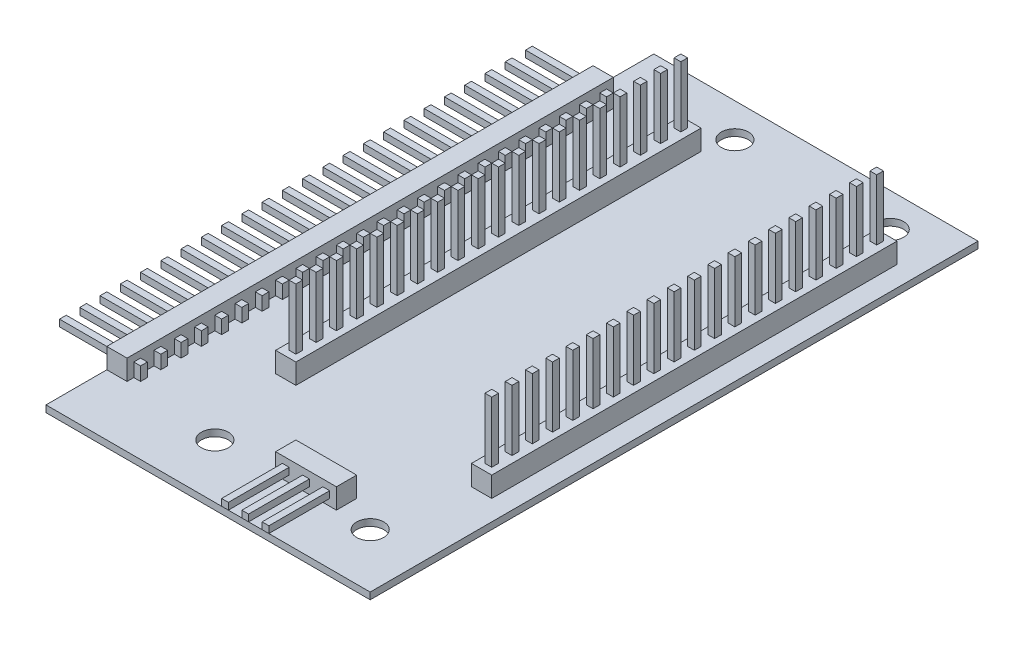
SolidWorks part; units mm, degrees
ref_plane "Front Plane" through (0, 0, 0) normal (0, 0, 1) x (1, 0, 0)
ref_plane "Top Plane" through (0, 0, 0) normal (0, 1, 0) x (1, 0, 0)
ref_plane "Right Plane" through (0, 0, 0) normal (1, 0, 0) x (0, 0, -1)
sketch "Sketch1" plane through (0, 0, 0) normal (0, 1, 0) x (1, 0, 0)
  line L1 (-19.05, 35.7188) -> (19.05, 35.7188)
  line L2 (-19.05, 35.7188) -> (-19.05, -35.7187)
  line L3 (-19.05, -35.7187) -> (19.05, -35.7187)
  line L4 (19.05, 35.7188) -> (19.05, -35.7187)
  line L5 (-19.05, 35.7188) -> (19.05, -35.7187) construction
  line L6 (-19.05, -35.7187) -> (19.05, 35.7188) construction
  point P0 (0, 0)
  dimension "D1" = 38.1
  dimension "D2" = 71.4375
extrude "Boss-Extrude1" add sketch "Sketch1" along normal blind 0.7937
sketch "Sketch2" plane through (0, 0.7937, 0) normal (0, 1, 0) x (1, 0, 0)
  line L0 (0, 0) -> (-19.05, 0) construction
  line L1 (-19.05, 35.7188) -> (-19.05, -35.7187) construction
  line L2 (-19.05, 4.7625) -> (-25.5985, 4.7625) construction
  line L3 (-15.875, 0.7937) -> (-25.4, 0.7937)
  line L4 (-15.875, 0.7937) -> (-15.875, 1.5875)
  line L5 (-15.875, 1.5875) -> (-25.4, 1.5875)
  line L6 (-25.4, 0.7937) -> (-25.4, 1.5875)
  line L7 (-25.4, 3.175) -> (-15.875, 3.175)
  line L8 (-25.4, 3.175) -> (-25.4, 3.9687)
  line L9 (-25.4, 3.9687) -> (-15.875, 3.9687)
  line L10 (-15.875, 3.175) -> (-15.875, 3.9687)
  line L11 (-15.875, 7.9375) -> (-25.4, 7.9375)
  line L12 (-25.4, 8.7312) -> (-25.4, 7.9375)
  line L13 (-15.875, 8.7312) -> (-25.4, 8.7312)
  line L14 (-15.875, 8.7312) -> (-15.875, 7.9375)
  line L15 (-25.4, 5.5562) -> (-15.875, 5.5562)
  line L16 (-15.875, 6.35) -> (-15.875, 5.5562)
  line L17 (-25.4, 6.35) -> (-15.875, 6.35)
  line L18 (-25.4, 6.35) -> (-25.4, 5.5562)
  line L19 (-19.05, 9.525) -> (-25.9028, 9.525) construction
  line L20 (-15.875, 10.3187) -> (-15.875, 11.1125)
  line L21 (-15.875, 10.3187) -> (-25.4, 10.3187)
  line L22 (-25.4, 10.3187) -> (-25.4, 11.1125)
  line L23 (-15.875, 11.1125) -> (-25.4, 11.1125)
  line L24 (-25.4, 12.7) -> (-25.4, 13.4937)
  line L25 (-25.4, 12.7) -> (-15.875, 12.7)
  line L26 (-15.875, 12.7) -> (-15.875, 13.4937)
  line L27 (-25.4, 13.4937) -> (-15.875, 13.4937)
  line L28 (-25.4, 15.0812) -> (-15.875, 15.0812)
  line L29 (-15.875, 15.875) -> (-15.875, 15.0812)
  line L30 (-25.4, 15.875) -> (-15.875, 15.875)
  line L31 (-25.4, 15.875) -> (-25.4, 15.0812)
  line L32 (-15.875, 17.4625) -> (-25.4, 17.4625)
  line L33 (-25.4, 18.2562) -> (-25.4, 17.4625)
  line L34 (-15.875, 18.2562) -> (-25.4, 18.2562)
  line L35 (-15.875, 18.2562) -> (-15.875, 17.4625)
  line L36 (-19.05, 19.05) -> (-25.9028, 19.05) construction
  line L37 (-15.875, 19.8437) -> (-15.875, 20.6375)
  line L38 (-15.875, 19.8437) -> (-25.4, 19.8437)
  line L39 (-25.4, 19.8437) -> (-25.4, 20.6375)
  line L40 (-15.875, 20.6375) -> (-25.4, 20.6375)
  line L41 (-25.4, 22.225) -> (-25.4, 23.0187)
  line L42 (-25.4, 22.225) -> (-15.875, 22.225)
  line L43 (-15.875, 22.225) -> (-15.875, 23.0187)
  line L44 (-25.4, 23.0187) -> (-15.875, 23.0187)
  line L45 (-25.4, 25.4) -> (-15.875, 25.4)
  line L46 (-15.875, 25.4) -> (-15.875, 24.6062)
  line L47 (-25.4, 24.6062) -> (-15.875, 24.6062)
  line L48 (-25.4, 25.4) -> (-25.4, 24.6062)
  line L49 (-15.875, 27.7812) -> (-25.4, 27.7812)
  line L50 (-25.4, 27.7812) -> (-25.4, 26.9875)
  line L51 (-15.875, 26.9875) -> (-25.4, 26.9875)
  line L52 (-15.875, 27.7812) -> (-15.875, 26.9875)
  line L53 (-19.05, -19.05) -> (-25.9028, -19.05) construction
  line L54 (-19.05, -9.525) -> (-25.9028, -9.525) construction
  line L55 (-19.05, -4.7625) -> (-25.5985, -4.7625) construction
  line L56 (-15.875, -27.7812) -> (-15.875, -26.9875)
  line L57 (-15.875, -26.9875) -> (-25.4, -26.9875)
  line L58 (-25.4, -27.7812) -> (-25.4, -26.9875)
  line L59 (-15.875, -27.7812) -> (-25.4, -27.7812)
  line L60 (-25.4, -25.4) -> (-25.4, -24.6062)
  line L61 (-25.4, -24.6062) -> (-15.875, -24.6062)
  line L62 (-15.875, -25.4) -> (-15.875, -24.6062)
  line L63 (-25.4, -25.4) -> (-15.875, -25.4)
  line L64 (-25.4, -23.0187) -> (-15.875, -23.0187)
  line L65 (-15.875, -22.225) -> (-15.875, -23.0187)
  line L66 (-25.4, -22.225) -> (-15.875, -22.225)
  line L67 (-25.4, -22.225) -> (-25.4, -23.0187)
  line L68 (-15.875, -20.6375) -> (-25.4, -20.6375)
  line L69 (-25.4, -19.8437) -> (-25.4, -20.6375)
  line L70 (-15.875, -19.8437) -> (-25.4, -19.8437)
  line L71 (-15.875, -19.8437) -> (-15.875, -20.6375)
  line L72 (-15.875, -18.2562) -> (-15.875, -17.4625)
  line L73 (-15.875, -18.2562) -> (-25.4, -18.2562)
  line L74 (-25.4, -18.2562) -> (-25.4, -17.4625)
  line L75 (-15.875, -17.4625) -> (-25.4, -17.4625)
  line L76 (-25.4, -15.875) -> (-25.4, -15.0812)
  line L77 (-25.4, -15.875) -> (-15.875, -15.875)
  line L78 (-15.875, -15.875) -> (-15.875, -15.0812)
  line L79 (-25.4, -15.0812) -> (-15.875, -15.0812)
  line L80 (-25.4, -13.4937) -> (-15.875, -13.4937)
  line L81 (-15.875, -12.7) -> (-15.875, -13.4937)
  line L82 (-25.4, -12.7) -> (-15.875, -12.7)
  line L83 (-25.4, -12.7) -> (-25.4, -13.4937)
  line L84 (-15.875, -11.1125) -> (-25.4, -11.1125)
  line L85 (-25.4, -10.3187) -> (-25.4, -11.1125)
  line L86 (-15.875, -10.3187) -> (-25.4, -10.3187)
  line L87 (-15.875, -10.3187) -> (-15.875, -11.1125)
  line L88 (-25.4, -6.35) -> (-25.4, -5.5562)
  line L89 (-25.4, -6.35) -> (-15.875, -6.35)
  line L90 (-15.875, -6.35) -> (-15.875, -5.5562)
  line L91 (-25.4, -5.5562) -> (-15.875, -5.5562)
  line L92 (-15.875, -8.7312) -> (-15.875, -7.9375)
  line L93 (-15.875, -8.7312) -> (-25.4, -8.7312)
  line L94 (-25.4, -8.7312) -> (-25.4, -7.9375)
  line L95 (-15.875, -7.9375) -> (-25.4, -7.9375)
  line L96 (-15.875, -3.175) -> (-15.875, -3.9687)
  line L97 (-25.4, -3.9687) -> (-15.875, -3.9687)
  line L98 (-25.4, -3.175) -> (-25.4, -3.9687)
  line L99 (-25.4, -3.175) -> (-15.875, -3.175)
  line L100 (-25.4, -0.7937) -> (-25.4, -1.5875)
  line L101 (-15.875, -1.5875) -> (-25.4, -1.5875)
  line L102 (-15.875, -0.7937) -> (-15.875, -1.5875)
  line L103 (-15.875, -0.7937) -> (-25.4, -0.7937)
  line L104 (-16.6688, 27.7812) -> (-16.6688, 26.9875)
  line L105 (-16.6688, -26.9875) -> (-16.6688, -27.7813)
  line L106 (-16.6688, -24.6062) -> (-16.6688, -25.4)
  line L107 (-16.6688, -22.225) -> (-16.6688, -23.0187)
  line L108 (-16.6688, -17.4625) -> (-16.6688, -20.6375)
  line L109 (-16.6688, -15.0812) -> (-16.6688, -15.875)
  line L110 (-16.6688, -12.7) -> (-16.6688, -13.4937)
  line L111 (-16.6688, -10.3187) -> (-16.6688, -11.1125)
  line L112 (-16.6688, -7.9375) -> (-16.6688, -8.7312)
  line L113 (-16.6688, -5.5562) -> (-16.6688, -6.35)
  line L114 (-16.6688, -3.175) -> (-16.6688, -3.9687)
  line L115 (-16.6688, -0.7937) -> (-16.6688, -1.5875)
  line L116 (-16.6688, 11.1125) -> (-16.6688, 10.3187)
  line L117 (-16.6688, 8.7312) -> (-16.6688, 7.9375)
  line L118 (-16.6688, 6.35) -> (-16.6688, 5.5562)
  line L119 (-16.6688, 3.9687) -> (-16.6688, 3.175)
  line L120 (-16.6688, 1.5875) -> (-16.6688, 0.7938)
  line L121 (-16.6688, 13.4937) -> (-16.6688, 12.7)
  line L122 (-16.6688, 15.875) -> (-16.6688, 15.0812)
  line L123 (-16.6688, 18.2562) -> (-16.6688, 17.4625)
  line L124 (-16.6688, 20.6375) -> (-16.6688, 19.8437)
  line L125 (-16.6688, 23.0187) -> (-16.6688, 22.225)
  line L126 (-16.6688, 25.4) -> (-16.6688, 24.6062)
  point P9 (-25.4, 1.1906)
  dimension "D1" = 3.175
  dimension "D2" = 6.35
  dimension "D3" = 0.7937
  dimension "D4" = 0.7937
  dimension "D5" = 1.5875
  dimension "D6" = 0.7937
  dimension "D7" = 0.7937
  dimension "D8" = 0.7937
  dimension "D9" = 0.7937
extrude "Boss-Extrude2" add sketch "Sketch2" along normal blind 0.7937 contours L49 L104 L51 L52 | L45 L126 L47 L46 | L44 L125 L42 L43 | L40 L124 L38 L37 | L34 L123 L32 L35 | L30 L122 L28 L29 | L27 L121 L25 L26 | L23 L116 L21 L20 | L13 L117 L11 L14 | L17 L118 L15 L16 | L9 L119 L7 L10 | L5 L120 L3 L4 | L103 L115 L101 L102 | L99 L114 L97 L96 | L91 L113 L89 L90 | L95 L112 L93 L92 | L86 L111 L84 L87 | L82 L110 L80 L81 | L79 L109 L77 L78 | L75 L108 L73 L72 | L70 L108 L68 L71 | L66 L107 L64 L65 | L61 L106 L63 L62 | L57 L105 L59 L56 region at (-16.2719, 0.7937, -1.1906) region at (-16.2719, 0.7937, -3.5719) region at (-16.2719, 0.7937, -8.3344) region at (-16.2719, 0.7937, -5.9531) region at (-16.2719, 0.7937, -10.7156) region at (-16.2719, 0.7937, -13.0969) region at (-16.2719, 0.7937, -15.4781) region at (-16.2719, 0.7937, -17.8594) region at (-16.2719, 0.7937, -20.2406) region at (-16.2719, 0.7937, -22.6219) region at (-16.2719, 0.7937, -25.0031) region at (-16.2719, 0.7937, -27.3844) region at (-16.2719, 0.7937, 27.3844) region at (-16.2719, 0.7937, 25.0031) region at (-16.2719, 0.7937, 22.6219) region at (-16.2719, 0.7937, 17.8594) region at (-16.2719, 0.7937, 20.2406) region at (-16.2719, 0.7937, 15.4781) region at (-16.2719, 0.7937, 13.0969) region at (-16.2719, 0.7937, 10.7156) region at (-16.2719, 0.7937, 5.9531) region at (-16.2719, 0.7937, 8.3344) region at (-16.2719, 0.7937, 3.5719) region at (-16.2719, 0.7937, 1.1906)
extrude "Boss-Extrude3" add sketch "Sketch2<3>" along normal blind 0.7937 from offset 0.7937 contours L51 L50 L49 L52 | L45 L46 L47 L48 | L44 L43 L42 L41 | L40 L39 L38 L37 | L34 L33 L32 L35 | L30 L29 L28 L31 | L27 L26 L25 L24 | L23 L22 L21 L20 | L13 L12 L11 L14 | L17 L16 L15 L18 | L9 L10 L7 L8 | L5 L6 L3 L4 | L103 L100 L101 L102 | L99 L96 L97 L98 | L91 L90 L89 L88 | L95 L94 L93 L92 | L86 L85 L84 L87 | L82 L81 L80 L83 | L79 L78 L77 L76 | L75 L74 L73 L72 | L70 L69 L68 L71 | L66 L65 L64 L67 | L61 L62 L63 L60 | L57 L58 L59 L56
sketch "Sketch2<3>" plane through (0, 0.7937, 0) normal (0, 1, 0) x (1, 0, 0) same geometry as "Sketch2"
sketch "Sketch3" plane through (0, 0.7937, 0) normal (0, 1, 0) x (1, 0, 0)
  line L0 (-19.05, 35.7188) -> (-19.05, -35.7187) construction
  line L1 (-19.05, 28.575) -> (-16.6688, 28.575)
  line L2 (-19.05, 28.575) -> (-19.05, -28.575)
  line L3 (-19.05, -28.575) -> (-16.6687, -28.575)
  line L4 (-16.6688, 28.575) -> (-16.6687, -28.575)
  line L5 (-15.875, 27.7812) -> (-25.4, 27.7812) construction
  line L6 (-15.875, -27.7812) -> (-25.4, -27.7812) construction
  dimension "D1" = 2.3813
  dimension "D2" = 0.7937
  dimension "D3" = 0.7937
extrude "Boss-Extrude4" add sketch "Sketch3" along normal blind 2.3813
sketch "Sketch4" plane through (0, 0.7937, 0) normal (0, 1, 0) x (1, 0, 0)
  line L0 (19.05, 4.7625) -> (-19.05, 4.7625) construction
  line L2 (19.05, -35.7187) -> (19.05, 35.7188) construction
  line L3 (-15.875, 27.7812) -> (-16.6688, 27.7812) construction
  line L4 (-7.9375, 25.4) -> (-7.1438, 25.4)
  line L5 (-7.9375, 25.4) -> (-7.9375, 24.6062)
  line L6 (-7.9375, 24.6062) -> (-7.1438, 24.6062)
  line L7 (-7.1438, 25.4) -> (-7.1438, 24.6062)
  line L8 (-7.9375, 23.0187) -> (-7.1438, 23.0187)
  line L9 (-7.9375, 23.0187) -> (-7.9375, 22.225)
  line L10 (-7.9375, 22.225) -> (-7.1438, 22.225)
  line L11 (-7.1438, 23.0187) -> (-7.1438, 22.225)
  line L12 (-7.9375, 20.6375) -> (-7.1438, 20.6375)
  line L13 (-7.9375, 20.6375) -> (-7.9375, 19.8437)
  line L14 (-7.9375, 19.8437) -> (-7.1438, 19.8437)
  line L15 (-7.1438, 20.6375) -> (-7.1438, 19.8437)
  line L16 (-7.9375, 18.2562) -> (-7.1438, 18.2562)
  line L17 (-7.9375, 18.2562) -> (-7.9375, 17.4625)
  line L18 (-7.9375, 17.4625) -> (-7.1438, 17.4625)
  line L19 (-7.1438, 18.2562) -> (-7.1438, 17.4625)
  line L20 (-7.9375, 15.875) -> (-7.1438, 15.875)
  line L21 (-7.9375, 15.875) -> (-7.9375, 15.0813)
  line L22 (-7.9375, 15.0813) -> (-7.1438, 15.0813)
  line L23 (-7.1438, 15.875) -> (-7.1438, 15.0813)
  line L24 (-7.9375, 13.4938) -> (-7.1438, 13.4937)
  line L25 (-7.9375, 13.4938) -> (-7.9375, 12.7)
  line L26 (-7.9375, 12.7) -> (-7.1438, 12.7)
  line L27 (-7.1438, 13.4937) -> (-7.1438, 12.7)
  line L28 (-7.9375, 11.1125) -> (-7.1438, 11.1125)
  line L29 (-7.9375, 11.1125) -> (-7.9375, 10.3187)
  line L30 (-7.9375, 10.3187) -> (-7.1438, 10.3187)
  line L31 (-7.1438, 11.1125) -> (-7.1438, 10.3187)
  line L32 (-7.9375, 8.7312) -> (-7.1438, 8.7312)
  line L33 (-7.9375, 8.7312) -> (-7.9375, 7.9375)
  line L34 (-7.9375, 7.9375) -> (-7.1438, 7.9375)
  line L35 (-7.1438, 8.7312) -> (-7.1438, 7.9375)
  line L36 (-7.9375, 27.7812) -> (-7.1438, 27.7812)
  line L37 (-7.9375, 27.7812) -> (-7.9375, 26.9875)
  line L38 (-7.9375, 26.9875) -> (-7.1438, 26.9875)
  line L39 (-7.1438, 27.7812) -> (-7.1438, 26.9875)
  line L40 (-7.9375, 6.35) -> (-7.1438, 6.35)
  line L41 (-7.9375, 6.35) -> (-7.9375, 5.5562)
  line L42 (-7.9375, 5.5562) -> (-7.1438, 5.5562)
  line L43 (-7.1438, 6.35) -> (-7.1438, 5.5562)
  line L44 (-19.05, 28.575) -> (-19.05, -28.575) construction
  line L45 (-7.1438, 3.175) -> (-7.1438, 3.9687)
  line L46 (-7.9375, 3.9687) -> (-7.1438, 3.9687)
  line L47 (-7.9375, 3.175) -> (-7.9375, 3.9687)
  line L48 (-7.9375, 3.175) -> (-7.1438, 3.175)
  line L49 (-7.1438, -18.2562) -> (-7.1438, -17.4625)
  line L50 (-7.9375, -17.4625) -> (-7.1438, -17.4625)
  line L51 (-7.9375, -18.2562) -> (-7.9375, -17.4625)
  line L52 (-7.9375, -18.2562) -> (-7.1438, -18.2562)
  line L53 (-7.1438, 0.7937) -> (-7.1438, 1.5875)
  line L54 (-7.9375, 1.5875) -> (-7.1438, 1.5875)
  line L55 (-7.9375, 0.7937) -> (-7.9375, 1.5875)
  line L56 (-7.9375, 0.7937) -> (-7.1438, 0.7937)
  line L57 (-7.1438, -1.5875) -> (-7.1438, -0.7938)
  line L58 (-7.9375, -0.7938) -> (-7.1438, -0.7938)
  line L59 (-7.9375, -1.5875) -> (-7.9375, -0.7938)
  line L60 (-7.9375, -1.5875) -> (-7.1438, -1.5875)
  line L61 (-7.1438, -3.9688) -> (-7.1438, -3.175)
  line L62 (-7.9375, -3.175) -> (-7.1438, -3.175)
  line L63 (-7.9375, -3.9688) -> (-7.9375, -3.175)
  line L64 (-7.9375, -3.9688) -> (-7.1438, -3.9688)
  line L65 (-7.1438, -6.35) -> (-7.1438, -5.5563)
  line L66 (-7.9375, -5.5563) -> (-7.1438, -5.5563)
  line L67 (-7.9375, -6.35) -> (-7.9375, -5.5563)
  line L68 (-7.9375, -6.35) -> (-7.1438, -6.35)
  line L69 (-7.1438, -8.7313) -> (-7.1438, -7.9375)
  line L70 (-7.9375, -7.9375) -> (-7.1438, -7.9375)
  line L71 (-7.9375, -8.7313) -> (-7.9375, -7.9375)
  line L72 (-7.9375, -8.7313) -> (-7.1438, -8.7313)
  line L73 (-7.1438, -11.1125) -> (-7.1438, -10.3188)
  line L74 (-7.9375, -10.3188) -> (-7.1438, -10.3188)
  line L75 (-7.9375, -11.1125) -> (-7.9375, -10.3188)
  line L76 (-7.9375, -11.1125) -> (-7.1438, -11.1125)
  line L77 (-7.1438, -13.4937) -> (-7.1438, -12.7)
  line L78 (-7.9375, -12.7) -> (-7.1438, -12.7)
  line L79 (-7.9375, -13.4937) -> (-7.9375, -12.7)
  line L80 (-7.9375, -13.4937) -> (-7.1438, -13.4937)
  line L81 (-7.1438, -15.875) -> (-7.1438, -15.0812)
  line L82 (-7.9375, -15.0812) -> (-7.1438, -15.0812)
  line L83 (-7.9375, -15.875) -> (-7.9375, -15.0812)
  line L84 (-7.9375, -15.875) -> (-7.1438, -15.875)
  line L85 (3.9688, 35.7188) -> (3.9688, -35.7187) construction
  line L86 (19.05, 35.7188) -> (-19.05, 35.7188) construction
  line L87 (-19.05, -35.7187) -> (19.05, -35.7187) construction
  line L88 (15.875, -15.875) -> (15.0813, -15.875)
  line L89 (15.875, -15.875) -> (15.875, -15.0812)
  line L90 (15.875, -15.0812) -> (15.0813, -15.0812)
  line L91 (15.0813, -15.875) -> (15.0813, -15.0812)
  line L92 (15.875, -13.4937) -> (15.0813, -13.4937)
  line L93 (15.875, -13.4937) -> (15.875, -12.7)
  line L94 (15.875, -12.7) -> (15.0813, -12.7)
  line L95 (15.0813, -13.4937) -> (15.0813, -12.7)
  line L96 (15.875, -11.1125) -> (15.0813, -11.1125)
  line L97 (15.875, -11.1125) -> (15.875, -10.3188)
  line L98 (15.875, -10.3188) -> (15.0813, -10.3188)
  line L99 (15.0813, -11.1125) -> (15.0813, -10.3188)
  line L100 (15.875, -8.7313) -> (15.0813, -8.7313)
  line L101 (15.875, -8.7313) -> (15.875, -7.9375)
  line L102 (15.875, -7.9375) -> (15.0813, -7.9375)
  line L103 (15.0813, -8.7313) -> (15.0813, -7.9375)
  line L104 (15.875, -6.35) -> (15.0813, -6.35)
  line L105 (15.875, -6.35) -> (15.875, -5.5563)
  line L106 (15.875, -5.5563) -> (15.0813, -5.5563)
  line L107 (15.0813, -6.35) -> (15.0813, -5.5563)
  line L108 (15.875, -3.9688) -> (15.0813, -3.9688)
  line L109 (15.875, -3.9688) -> (15.875, -3.175)
  line L110 (15.875, -3.175) -> (15.0813, -3.175)
  line L111 (15.0813, -3.9688) -> (15.0813, -3.175)
  line L112 (15.875, -1.5875) -> (15.0813, -1.5875)
  line L113 (15.875, -1.5875) -> (15.875, -0.7938)
  line L114 (15.875, -0.7938) -> (15.0813, -0.7938)
  line L115 (15.0813, -1.5875) -> (15.0813, -0.7938)
  line L116 (15.875, 0.7937) -> (15.0813, 0.7937)
  line L117 (15.875, 0.7937) -> (15.875, 1.5875)
  line L118 (15.875, 1.5875) -> (15.0813, 1.5875)
  line L119 (15.0813, 0.7937) -> (15.0813, 1.5875)
  line L120 (15.875, -18.2562) -> (15.0813, -18.2562)
  line L121 (15.875, -18.2562) -> (15.875, -17.4625)
  line L122 (15.875, -17.4625) -> (15.0813, -17.4625)
  line L123 (15.0813, -18.2562) -> (15.0813, -17.4625)
  line L124 (15.875, 3.175) -> (15.0813, 3.175)
  line L125 (15.875, 3.175) -> (15.875, 3.9687)
  line L126 (15.875, 3.9687) -> (15.0813, 3.9687)
  line L127 (15.0813, 3.175) -> (15.0813, 3.9687)
  line L128 (15.0813, 6.35) -> (15.0813, 5.5562)
  line L129 (15.875, 5.5563) -> (15.0813, 5.5562)
  line L130 (15.875, 6.35) -> (15.875, 5.5563)
  line L131 (15.875, 6.35) -> (15.0813, 6.35)
  line L132 (15.0813, 27.7812) -> (15.0813, 26.9875)
  line L133 (15.875, 26.9875) -> (15.0813, 26.9875)
  line L134 (15.875, 27.7812) -> (15.875, 26.9875)
  line L135 (15.875, 27.7812) -> (15.0813, 27.7812)
  line L136 (15.0813, 8.7312) -> (15.0813, 7.9375)
  line L137 (15.875, 7.9375) -> (15.0813, 7.9375)
  line L138 (15.875, 8.7313) -> (15.875, 7.9375)
  line L139 (15.875, 8.7313) -> (15.0813, 8.7312)
  line L140 (15.0813, 11.1125) -> (15.0813, 10.3187)
  line L141 (15.875, 10.3188) -> (15.0813, 10.3187)
  line L142 (15.875, 11.1125) -> (15.875, 10.3188)
  line L143 (15.875, 11.1125) -> (15.0813, 11.1125)
  line L144 (15.0813, 13.4937) -> (15.0813, 12.7)
  line L145 (15.875, 12.7) -> (15.0813, 12.7)
  line L146 (15.875, 13.4938) -> (15.875, 12.7)
  line L147 (15.875, 13.4938) -> (15.0813, 13.4937)
  line L148 (15.0813, 15.875) -> (15.0813, 15.0813)
  line L149 (15.875, 15.0813) -> (15.0813, 15.0813)
  line L150 (15.875, 15.875) -> (15.875, 15.0813)
  line L151 (15.875, 15.875) -> (15.0813, 15.875)
  line L152 (15.0813, 18.2562) -> (15.0813, 17.4625)
  line L153 (15.875, 17.4625) -> (15.0813, 17.4625)
  line L154 (15.875, 18.2563) -> (15.875, 17.4625)
  line L155 (15.875, 18.2563) -> (15.0813, 18.2562)
  line L156 (15.0813, 20.6375) -> (15.0813, 19.8437)
  line L157 (15.875, 19.8438) -> (15.0813, 19.8437)
  line L158 (15.875, 20.6375) -> (15.875, 19.8438)
  line L159 (15.875, 20.6375) -> (15.0813, 20.6375)
  line L160 (15.0813, 23.0187) -> (15.0813, 22.225)
  line L161 (15.875, 22.225) -> (15.0813, 22.225)
  line L162 (15.875, 23.0187) -> (15.875, 22.225)
  line L163 (15.875, 23.0187) -> (15.0813, 23.0187)
  line L164 (15.0813, 25.4) -> (15.0813, 24.6062)
  line L165 (15.875, 24.6062) -> (15.0813, 24.6062)
  line L166 (15.875, 25.4) -> (15.875, 24.6062)
  line L167 (15.875, 25.4) -> (15.0813, 25.4)
  dimension "D2" = 1.5875
  dimension "D3" = 1.5875
  dimension "D4" = 1.5875
  dimension "D5" = 1.5875
  dimension "D6" = 1.5875
  dimension "D7" = 1.5875
  dimension "D8" = 1.5875
  dimension "D9" = 1.5875
  dimension "D10" = 1.5875
  dimension "D11" = 26.1937
  dimension "D12" = 0.7937
  dimension "D13" = 0.7937
  dimension "D14" = 11.1125
extrude "Boss-Extrude5" add sketch "Sketch4" along normal blind 9.525
sketch "Sketch5" plane through (0, 0.7937, 0) normal (0, 1, 0) x (1, 0, 0)
  line L0 (-7.1438, 27.7812) -> (-7.9375, 27.7812) construction
  line L1 (-8.7313, 28.575) -> (-6.35, 28.575)
  line L2 (-8.7313, 28.575) -> (-8.7313, -19.05)
  line L3 (-8.7313, -19.05) -> (-6.35, -19.05)
  line L4 (-6.35, 28.575) -> (-6.35, -19.05)
  line L5 (14.2875, 28.575) -> (16.6688, 28.575)
  line L6 (14.2875, 28.575) -> (14.2875, -19.05)
  line L7 (14.2875, -19.05) -> (16.6688, -19.05)
  line L8 (16.6688, 28.575) -> (16.6688, -19.05)
  line L9 (-7.9375, -18.2562) -> (-7.1438, -18.2562) construction
  line L10 (15.0813, -18.2562) -> (15.875, -18.2562) construction
  point P10 (-7.5406, 27.7812)
  point P11 (-7.5406, 28.575)
  point P16 (15.4781, -18.2562)
  point P17 (15.4781, -19.05)
  dimension "D1" = 2.3813
  dimension "D2" = 0.7937
  dimension "D3" = 0.7937
  dimension "D4" = 2.3813
extrude "Boss-Extrude6" add sketch "Sketch5" along normal blind 2.3813
sketch "Sketch6" plane through (0, 0.7937, 0) normal (0, 1, 0) x (1, 0, 0)
  line L0 (-19.05, -35.7187) -> (19.05, -35.7187) construction
  line L1 (2.3813, -26.1937) -> (3.175, -26.1937)
  line L2 (2.3813, -26.1937) -> (2.3813, -36.5125)
  line L3 (2.3813, -36.5125) -> (3.175, -36.5125)
  line L4 (3.175, -26.1937) -> (3.175, -36.5125)
  line L5 (4.7625, -26.1937) -> (5.5563, -26.1937)
  line L6 (4.7625, -26.1937) -> (4.7625, -36.5125)
  line L7 (4.7625, -36.5125) -> (5.5563, -36.5125)
  line L8 (5.5563, -26.1937) -> (5.5563, -36.5125)
  line L9 (7.1438, -26.1937) -> (7.9375, -26.1937)
  line L10 (7.1438, -26.1937) -> (7.1438, -36.5125)
  line L11 (7.1438, -36.5125) -> (7.9375, -36.5125)
  line L12 (7.9375, -26.1937) -> (7.9375, -36.5125)
  line L13 (2.3813, -26.9875) -> (3.175, -26.9875)
  line L14 (4.7625, -26.9875) -> (5.5563, -26.9875)
  line L15 (7.1438, -26.9875) -> (7.9375, -26.9875)
  line L16 (19.05, -35.7187) -> (19.05, 35.7188) construction
  dimension "D1" = 1.5875
  dimension "D2" = 1.5875
  dimension "D3" = 10.3187
  dimension "D4" = 9.525
  dimension "D5" = 0.7937
  dimension "D6" = 11.1125
  dimension "D7" = 0.7937
extrude "Boss-Extrude7" add sketch "Sketch6" along normal blind 0.7937 contours L2 L13 L4 L1 | L6 L14 L8 L5 | L10 L15 L12 L9 region at (2.7781, 0.7937, 26.5906) region at (5.1594, 0.7937, 26.5906) region at (7.5406, 0.7937, 26.5906)
extrude "Boss-Extrude8" add sketch "Sketch6<3>" along normal blind 0.7937 from offset 0.7937 contours L2 L3 L4 L1 | L6 L7 L8 L5 | L10 L11 L12 L9
sketch "Sketch6<3>" plane through (0, 0.7937, 0) normal (0, 1, 0) x (1, 0, 0) same geometry as "Sketch6"
sketch "Sketch7" plane through (0, 0.7937, 0) normal (0, 1, 0) x (1, 0, 0)
  line L0 (4.7625, -26.1937) -> (5.5563, -26.1937) construction
  line L1 (1.5875, -26.9875) -> (8.7313, -26.9875)
  line L2 (1.5875, -26.9875) -> (1.5875, -29.3687)
  line L3 (1.5875, -29.3687) -> (8.7313, -29.3687)
  line L4 (8.7313, -26.9875) -> (8.7313, -29.3687)
  line L5 (2.3813, -26.1937) -> (2.3813, -36.5125) construction
  line L6 (7.9375, -26.1937) -> (7.9375, -36.5125) construction
  dimension "D1" = 0.7937
  dimension "D2" = 2.3813
  dimension "D3" = 0.7937
  dimension "D4" = 0.7937
extrude "Boss-Extrude9" add sketch "Sketch7" along normal blind 2.3813
sketch "Sketch8" plane through (0, 0.7937, 0) normal (0, 1, 0) x (1, 0, 0)
  line L0 (19.05, 35.7188) -> (-19.05, 35.7188) construction
  line L1 (-5.5563, 31.75) -> (12.7, 31.75) construction
  line L2 (-5.5563, 31.75) -> (-5.5562, -29.3687) construction
  line L3 (-5.5562, -29.3687) -> (12.7, -29.3687) construction
  line L4 (12.7, 31.75) -> (12.7, -29.3687) construction
  line L5 (-5.5563, 31.75) -> (12.7, -29.3687) construction
  line L6 (-5.5562, -29.3687) -> (12.7, 31.75) construction
  line L7 (-19.05, -35.7187) -> (19.05, -35.7187) construction
  line L8 (19.05, -35.7187) -> (19.05, 35.7188) construction
  line L9 (-19.05, 35.7188) -> (-19.05, 28.575) construction
  circle A0 centre (-5.5563, 31.75) radius 1.5875
  circle A1 centre (12.7, 31.75) radius 1.5875
  circle A2 centre (-5.5562, -29.3687) radius 1.5875
  circle A3 centre (12.7, -29.3687) radius 1.5875
  point P0 (3.5719, 1.1906)
  dimension "D5" = 3.175
  dimension "D1" = 3.9688
  dimension "D2" = 6.35
  dimension "D3" = 6.35
  dimension "D4" = 13.4937
extrude "Cut-Extrude1" cut sketch "Sketch8" against normal through all
